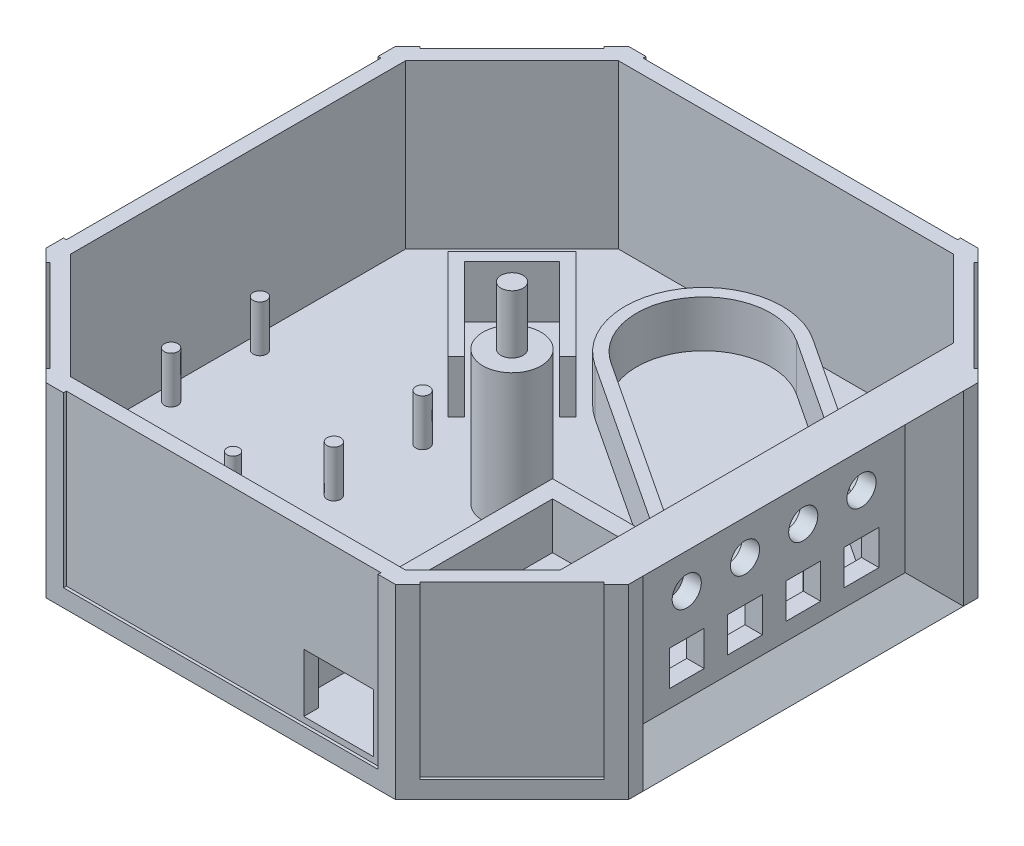
SolidWorks part; units mm, degrees
ref_plane "Front Plane" through (0, 0, 0) normal (0, 0, 1) x (1, 0, 0)
ref_plane "Top Plane" through (0, 0, 0) normal (0, 1, 0) x (1, 0, 0)
ref_plane "Right Plane" through (0, 0, 0) normal (1, 0, 0) x (0, 0, -1)
sketch "Sketch1" plane through (0, 0, 0) normal (0, 1, 0) x (1, 0, 0)
  line L0 (-30, 50) -> (-50, 30)
  line L1 (-50, 50) -> (50, 50)
  line L2 (-50, 50) -> (-50, -50)
  line L3 (-50, -50) -> (50, -50)
  line L4 (50, 50) -> (50, -50)
  line L5 (-50, 50) -> (50, -50) construction
  line L6 (-50, -50) -> (50, 50) construction
  line L7 (30, 50) -> (50, 30)
  line L8 (-50, -30) -> (-30, -50)
  line L9 (30, -50) -> (50, -30)
  point P0 (0, 0)
  dimension "D1" = 100
  dimension "D2" = 100
  dimension "D3" = 20
  dimension "D4" = 20
  dimension "D5" = 80
  dimension "D6" = 80
extrude "Boss-Extrude1" add sketch "Sketch1" along normal blind 32 contours L3 L9 L4 L7 L1 L0 L2 L8
sketch "Sketch2" plane through (0, 32, 0) normal (0, 1, 0) x (1, 0, 0)
  line L0 (-28.7574, -47) -> (28.7574, -47)
  line L1 (28.7574, -47) -> (47, -28.7574)
  line L2 (47, -28.7574) -> (47, 28.7574)
  line L3 (47, 28.7574) -> (28.7574, 47)
  line L4 (28.7574, 47) -> (-28.7574, 47)
  line L5 (-28.7574, 47) -> (-47, 28.7574)
  line L6 (-47, 28.7574) -> (-47, -28.7574)
  line L7 (-47, -28.7574) -> (-28.7574, -47)
  line L8 (-30, -50) -> (30, -50)
  line L9 (30, -50) -> (50, -30)
  line L10 (50, -30) -> (50, 30)
  line L11 (50, 30) -> (30, 50)
  line L12 (30, 50) -> (-30, 50)
  line L13 (-30, 50) -> (-50, 30)
  line L14 (-50, 30) -> (-50, -30)
  line L15 (-50, -30) -> (-30, -50)
  line L16 (-30, -50) -> (30, -50) construction
  line L17 (30, -50) -> (50, -30) construction
  line L18 (50, -30) -> (50, 30) construction
  line L19 (50, 30) -> (30, 50) construction
  line L20 (30, 50) -> (-30, 50) construction
  line L21 (-30, 50) -> (-50, 30) construction
  line L22 (-50, 30) -> (-50, -30) construction
  line L23 (-50, -30) -> (-30, -50) construction
  dimension "D1" = 0
  dimension "D2" = 3
extrude "Cut-Extrude1" cut sketch "Sketch2" against normal blind 28
sketch "Sketch3" plane through (0, 4, 0) normal (0, 1, 0) x (1, 0, 0)
  circle A1 centre (0, 0) radius 5
  dimension "D2" = 10
extrude "Boss-Extrude2" add sketch "Sketch3" along normal blind 23
sketch "Sketch4" plane through (0, 27, 0) normal (0, 1, 0) x (1, 0, 0)
  circle A0 centre (0, 0) radius 1.9
  dimension "D1" = 3.8
extrude "Boss-Extrude3" add sketch "Sketch4" along normal blind 10
sketch "Sketch5" plane through (0, 4, 0) normal (0, 1, 0) x (1, 0, 0)
  line L0 (0, 0) -> (-16.9706, 16.9706) construction
  line L1 (0, 0) -> (-47, 0) construction
  line L2 (-47, 28.7574) -> (-47, -28.7574) construction
  line L3 (-16.9706, 8.8388) -> (-31.1127, 22.981)
  line L4 (-31.1127, 22.981) -> (-22.981, 31.1127)
  line L5 (-22.981, 31.1127) -> (-8.8388, 16.9706)
  line L6 (-16.9706, 8.8388) -> (-8.8388, 16.9706) construction
  line L7 (-18.3848, 7.4246) -> (-33.9411, 22.981)
  line L8 (-33.9411, 22.981) -> (-22.981, 33.9411)
  line L9 (-22.981, 33.9411) -> (-7.4246, 18.3848)
  line L10 (-18.3848, 7.4246) -> (-16.9706, 8.8388)
  line L11 (-8.8388, 16.9706) -> (-7.4246, 18.3848)
  circle A0 centre (-16.9706, 16.9706) radius 20 construction
  circle A1 centre (-16.9706, 16.9706) radius 5.75 construction
  dimension "D2" = 40
  dimension "D1" = 24
  dimension "D3" = 45
  dimension "D4" = 11.5
  dimension "D5" = 20
  dimension "D6" = 2
extrude "Boss-Extrude4" add sketch "Sketch5" along normal blind 9
sketch "Sketch6" plane through (0, 4, 0) normal (0, 1, 0) x (1, 0, 0)
  line L9 (28.7574, -47) -> (47, -28.7574) construction
  line L10 (47, -28.7574) -> (47, 28.7574) construction
  line L11 (47, 28.7574) -> (28.7574, 47) construction
  line L12 (42, -33.7574) -> (47, -28.7574)
  line L13 (47, -28.7574) -> (47, 28.7574)
  line L14 (47, 28.7574) -> (42, 33.7574)
  line L15 (42, 33.7574) -> (42, -33.7574)
  dimension "D1" = 5
extrude "Boss-Extrude6" add sketch "Sketch6" along normal blind 28
sketch "Sketch7" plane through (50, 0, 0) normal (1, 0, 0) x (0, 0, -1)
  line L0 (-30, 32) -> (-30, 0) construction
  line L1 (22.5, 27) -> (-22.5, 27)
  line L2 (22.5, 27) -> (22.5, 5)
  line L3 (22.5, 5) -> (-22.5, 5)
  line L4 (-22.5, 27) -> (-22.5, 5)
  point P4 (0, 5)
  point P9 (-30, 16)
  point P10 (-22.5, 16)
  dimension "D1" = 45
  dimension "D2" = 22
extrude "Cut-Extrude2" cut sketch "Sketch7" against normal blind 5
chamfer "Chamfer1" distance 5 distance2 5 4 edges at (50, 16, 22.5) (50, 27, 0) (50, 16, -22.5) (50, 5, 0)
sketch "Sketch8" plane through (45, 0, 0) normal (1, 0, 0) x (0, 0, -1)
  line L0 (-22.5, 5) -> (22.5, 5) construction
  line L1 (-18, 14) -> (-12, 14)
  line L2 (-18, 14) -> (-18, 8)
  line L3 (-18, 8) -> (-12, 8)
  line L4 (-12, 14) -> (-12, 8)
  line L5 (-18, 14) -> (-12, 8) construction
  line L6 (-18, 8) -> (-12, 14) construction
  line L7 (-8, 14) -> (-2, 14)
  line L8 (-8, 14) -> (-8, 8)
  line L9 (-8, 8) -> (-2, 8)
  line L10 (-2, 14) -> (-2, 8)
  line L11 (-8, 14) -> (-2, 8) construction
  line L12 (-8, 8) -> (-2, 14) construction
  line L13 (2, 14) -> (8, 14)
  line L14 (2, 14) -> (2, 8)
  line L15 (2, 8) -> (8, 8)
  line L16 (8, 14) -> (8, 8)
  line L17 (2, 14) -> (8, 8) construction
  line L18 (2, 8) -> (8, 14) construction
  line L19 (12, 14) -> (18, 14)
  line L20 (12, 14) -> (12, 8)
  line L21 (12, 8) -> (18, 8)
  line L22 (18, 14) -> (18, 8)
  line L23 (12, 14) -> (18, 8) construction
  line L24 (12, 8) -> (18, 14) construction
  circle A0 centre (-15, 21) radius 2.5
  circle A1 centre (-5, 21) radius 2.5
  circle A2 centre (5, 21) radius 2.5
  circle A3 centre (15, 21) radius 2.5
  point P8 (-15, 11)
  point P13 (-5, 11)
  point P18 (5, 11)
  point P23 (15, 11)
  dimension "D1" = 5
  dimension "D2" = 10
  dimension "D3" = 10
  dimension "D4" = 10
  dimension "D5" = 5
  dimension "D6" = 6
  dimension "D7" = 6
  dimension "D8" = 10
extrude "Cut-Extrude3" cut sketch "Sketch8" against normal blind 5
sketch "Sketch10" plane through (0, 4, 0) normal (0, 1, 0) x (1, 0, 0)
  line L0 (-28.7574, -47) -> (28.7574, -47) construction
  line L1 (28.7574, -47) -> (10.7574, -47)
  line L2 (28.7574, -47) -> (28.7574, -3.8)
  line L3 (28.7574, -3.8) -> (10.7574, -3.8)
  line L4 (10.7574, -47) -> (10.7574, -3.8)
  line L5 (-47, 28.7574) -> (-47, -28.7574) construction
  line L6 (-26.2786, -21.6) -> (7.7574, -21.6) construction
  line L7 (-26.2786, -21.6) -> (-26.2786, -47) construction
  line L8 (-26.2786, -47) -> (7.7574, -47) construction
  line L9 (7.7574, -21.6) -> (7.7574, -47)
  line L10 (-47, 3.72) -> (-13.98, 3.72) construction
  line L11 (-47, 3.72) -> (-47, -16.6) construction
  line L12 (-47, -16.6) -> (-13.98, -16.6) construction
  line L13 (-13.98, 3.72) -> (-13.98, -16.6) construction
  line L14 (8.1695, 40.6777) -> (42, 18.4124)
  line L15 (-44.46, 1.18) -> (-16.52, 1.18) construction
  line L16 (-44.46, 1.18) -> (-44.46, -14.06) construction
  line L17 (-44.46, -14.06) -> (-16.52, -14.06) construction
  line L18 (-16.52, 1.18) -> (-16.52, -14.06) construction
  line L19 (-14.0812, 27.7876) -> (-10.3817, 25.3527)
  line L20 (7.7574, -47) -> (31.7574, -47)
  line L21 (7.7574, -47) -> (7.7574, -0.8)
  line L22 (7.7574, -0.8) -> (31.7574, -0.8)
  line L23 (31.7574, -47) -> (31.7574, -0.8)
  line L28 (-14.0812, 27.7876) -> (-11.6464, 31.4872)
  line L29 (29.3555, -0.8) -> (42, 18.4124) construction
  line L30 (-1.4367, 47) -> (2.2629, 44.5651)
  line L31 (42, 33.7574) -> (42, -33.7574) construction
  line L32 (28.7574, 47) -> (-28.7574, 47) construction
  line L33 (-1.4367, 47) -> (42, 18.4124) construction
  line L34 (42, 33.7574) -> (42, -33.7574) construction
  line L35 (-16.8514, 27.2165) -> (29.9266, -3.5702)
  line L36 (29.9266, -3.5702) -> (44.7702, 18.9835) construction
  line L37 (-2.0078, 49.7702) -> (44.7702, 18.9835)
  line L38 (-16.8514, 27.2165) -> (-2.0078, 49.7702)
  line L39 (42, 18.4124) -> (44.7702, 18.9835)
  line L40 (-3.8716, 43.3004) -> (-1.4367, 47)
  line L41 (-14.0812, 27.7876) -> (-1.4367, 47) construction
  line L42 (-4.475, 21.4653) -> (29.3555, -0.8)
  line L43 (-14.0812, 27.7876) -> (29.3555, -0.8) construction
  circle A0 centre (-23.7386, -24.14) radius 1.043
  circle A1 centre (-23.7386, -44.46) radius 1.043
  circle A2 centre (-44.46, 1.18) radius 1.17
  circle A3 centre (-16.52, 1.18) radius 1.17
  circle A4 centre (-16.52, -14.06) radius 1.17
  circle A5 centre (-44.46, -14.06) radius 1.17
  arc A6 (8.1695, 40.6777) -> (-4.475, 21.4653) centre (1.8472, 31.0715) ccw
  arc A7 (9.269, 42.3484) -> (-5.5746, 19.7947) centre (1.8472, 31.0715) ccw
  circle A8 centre (1.8472, 31.0715) radius 13.5 construction
  circle A9 centre (1.8472, 31.0715) radius 11.5 construction
  dimension "D10" = 2.086
  dimension "D11" = 2.34
  dimension "D1" = 43.2
  dimension "D2" = 18
  dimension "D3" = 25.4
  dimension "D4" = 34.036
  dimension "D5" = 33.02
  dimension "D6" = 20.32
  dimension "D7" = 2.54
  dimension "D8" = 2.54
  dimension "D9" = 2.54
  dimension "D12" = 3
  dimension "D13" = 3
  dimension "D14" = 3
  dimension "D15" = 5
  dimension "D16" = 2.54
  dimension "D17" = 2.54
  dimension "D18" = 2.54
  dimension "D19" = 2.54
  dimension "D20" = 52
  dimension "D21" = 23
  dimension "D22" = 2
extrude "Boss-Extrude8" add sketch "Sketch10" along normal blind 8
sketch "Sketch11" plane through (0, 0, 47) normal (0, 0, -1) x (-1, 0, 0)
  line L0 (-10.7574, 4) -> (-28.7574, 4) construction
  line L1 (-25.7574, 4) -> (-13.7574, 4)
  line L2 (-25.7574, 4) -> (-25.7574, 14)
  line L3 (-25.7574, 14) -> (-13.7574, 14)
  line L4 (-13.7574, 4) -> (-13.7574, 14)
  line L6 (-10.7574, 12) -> (-28.7574, 12) construction
  point P10 (-19.7574, 4)
  point P11 (-19.7574, 12)
  point P14 (-19.7574, 14)
  dimension "D1" = 12
  dimension "D2" = 10
extrude "Cut-Extrude4" cut sketch "Sketch11" against normal blind 8
sketch "Sketch12" plane through (0, 4, 0) normal (0, 1, 0) x (1, 0, 0)
  line L0 (-28.7574, -47) -> (28.7574, -47) construction
  line L1 (14.7574, -15) -> (24.7574, -15)
  line L2 (14.7574, -15) -> (14.7574, -25)
  line L3 (14.7574, -25) -> (24.7574, -25)
  line L4 (24.7574, -15) -> (24.7574, -25)
  line L6 (10.7574, -47) -> (10.7574, -3.8) construction
  dimension "D1" = 32
  dimension "D2" = 14
  dimension "D3" = 10
  dimension "D4" = 10
extrude "Cut-Extrude5" cut sketch "Sketch12" against normal blind 8
ref_plane "Plane1" through (-40, 0, 40) normal (-0.7071, 0, 0.7071) x (0.7071, 0, 0.7071)
sketch "Sketch15" plane through (-40, 0, 40) normal (-0.7071, 0, 0.7071) x (0.7071, 0, 0.7071)
  line L1 (-14.1421, 32) -> (-11.1421, 32)
  line L2 (-14.1421, 32) -> (-14.1421, 0)
  line L3 (-14.1421, 0) -> (-11.1421, 0)
  line L4 (-14.1421, 0) -> (14.1421, 0)
  line L5 (14.1421, 0) -> (14.1421, 32)
  line L6 (14.1421, 32) -> (-14.1421, 32)
  line L7 (-14.1421, 32) -> (-14.1421, 0)
  line L8 (-14.1421, 0) -> (14.1421, 0)
  line L9 (14.1421, 0) -> (14.1421, 32)
  line L10 (14.1421, 32) -> (-14.1421, 32)
  line L11 (-14.1421, 32) -> (-14.1421, 0)
  line L12 (-11.1421, 32) -> (-11.1421, 0)
  line L13 (-14.1421, 0) -> (14.1421, 0)
  line L14 (-14.1421, 0) -> (-14.1421, 3)
  line L15 (-14.1421, 3) -> (14.1421, 3)
  line L16 (14.1421, 0) -> (14.1421, 3)
  line L17 (14.1421, 0) -> (11.1421, 0)
  line L18 (14.1421, 0) -> (14.1421, 32)
  line L19 (14.1421, 32) -> (11.1421, 32)
  line L20 (11.1421, 0) -> (11.1421, 32)
  dimension "D2" = 3
  dimension "D3" = 3
  dimension "D4" = 3
  dimension "D1" = 0
sketch "Sketch16" plane through (-40, 0, -40) normal (-0.7071, 0, -0.7071) x (-0.7071, 0, 0.7071)
  line L0 (-14.1421, 32) -> (14.1421, 32) construction
  line L1 (-11.1421, 32) -> (11.1421, 32)
  line L2 (-11.1421, 32) -> (-11.1421, 3)
  line L3 (-11.1421, 3) -> (11.1421, 3)
  line L4 (11.1421, 32) -> (11.1421, 3)
  line L5 (-14.1421, 32) -> (-14.1421, 0) construction
  line L6 (-14.1421, 0) -> (14.1421, 0) construction
  line L7 (14.1421, 32) -> (14.1421, 0) construction
  dimension "D1" = 3
  dimension "D2" = 3
  dimension "D3" = 3
extrude "Cut-Extrude6" cut sketch "Sketch16" against normal blind 0.5
sketch "Sketch17" plane through (0, 0, -50) normal (0, 0, -1) x (-1, 0, 0)
  line L0 (30, 32) -> (-30, 32) construction
  line L1 (-27, 32) -> (27, 32)
  line L2 (-27, 32) -> (-27, 3)
  line L3 (-27, 3) -> (27, 3)
  line L4 (27, 32) -> (27, 3)
  line L5 (-30, 32) -> (-30, 0) construction
  line L6 (30, 0) -> (-30, 0) construction
  line L7 (30, 32) -> (30, 0) construction
  dimension "D1" = 3
  dimension "D2" = 3
  dimension "D3" = 3
extrude "Cut-Extrude7" cut sketch "Sketch17" against normal blind 0.5
sketch "Sketch18" plane through (40, 0, -40) normal (0.7071, 0, -0.7071) x (-0.7071, 0, -0.7071)
  line L0 (14.1421, 32) -> (-14.1421, 32) construction
  line L1 (-11.1421, 32) -> (11.1421, 32)
  line L2 (-11.1421, 32) -> (-11.1421, 3)
  line L3 (-11.1421, 3) -> (11.1421, 3)
  line L4 (11.1421, 32) -> (11.1421, 3)
  line L5 (-14.1421, 32) -> (-14.1421, 0) construction
  line L6 (14.1421, 0) -> (-14.1421, 0) construction
  line L7 (14.1421, 32) -> (14.1421, 0) construction
  dimension "D1" = 3
  dimension "D2" = 3
  dimension "D3" = 3
extrude "Cut-Extrude8" cut sketch "Sketch18" against normal blind 0.5
ref_plane "Plane2" through (0, 0, 0) normal (0, 0, 1) x (1, 0, 0)
mirror "Mirror1" about plane through (0, 0, 0) normal (0, 0, 1) of "Cut-Extrude8", "Cut-Extrude7", "Cut-Extrude6"
sketch "Sketch19" plane through (-50, 0, 0) normal (-1, 0, 0) x (0, 0, 1)
  line L0 (-30, 32) -> (30, 32) construction
  line L1 (-27, 32) -> (27, 32)
  line L2 (-27, 32) -> (-27, 3)
  line L3 (-27, 3) -> (27, 3)
  line L4 (27, 32) -> (27, 3)
  line L5 (-30, 32) -> (-30, 0) construction
  line L6 (-30, 0) -> (30, 0) construction
  line L7 (30, 32) -> (30, 0) construction
  dimension "D1" = 3
  dimension "D2" = 3
  dimension "D3" = 3
extrude "Cut-Extrude9" cut sketch "Sketch19" against normal blind 0.5
